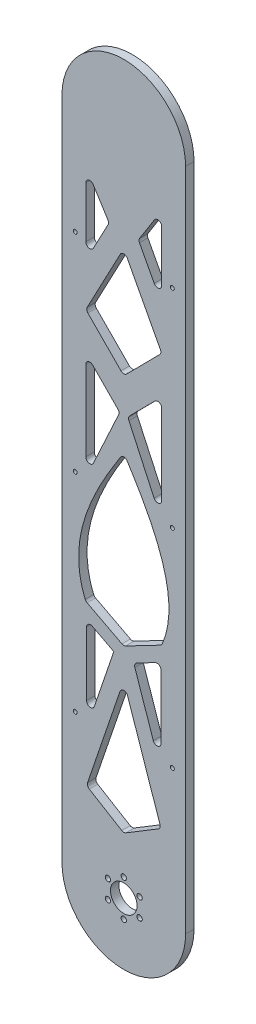
SolidWorks part; units mm, degrees
material "1060 Alloy"
ref_plane "Front Plane" through (0, 0, 0) normal (0, 0, 1) x (1, 0, 0)
ref_plane "Top Plane" through (0, 0, 0) normal (0, 1, 0) x (1, 0, 0)
ref_plane "Right Plane" through (0, 0, 0) normal (1, 0, 0) x (0, 0, -1)
sketch "Sketch2" plane through (0, 0, 0) normal (0, 0, 1) x (1, 0, 0)
  line L0 (0, 0) -> (0, 500) construction
  line L1 (-46.5, 0) -> (-46.5, 500)
  line L2 (46.5, 0) -> (46.5, 500)
  arc A0 (-46.5, 0) -> (46.5, 0) centre (0, 0) ccw
  arc A1 (46.5, 500) -> (-46.5, 500) centre (0, 500) ccw
  circle A2 centre (0, 500) radius 37.25 construction
  circle A3 centre (0, 0) radius 10
  circle A4 centre (0, 13.75) radius 2
  circle A5 centre (0, 0) radius 13.75 construction
  circle A6 centre (11.9078, 6.875) radius 2
  circle A7 centre (11.9078, -6.875) radius 2
  circle A8 centre (0, -13.75) radius 2
  circle A9 centre (-11.9078, -6.875) radius 2
  circle A10 centre (-11.9078, 6.875) radius 2
  point P3 (0, 250)
  point P27 (0, 0)
  dimension "D2" = 74.5
  dimension "D4" = 20
  dimension "D5" = 4
  dimension "D6" = 27.5
  dimension "D3" = 46.5
  dimension "D1" = 500
  dimension "D7" = 6
extrude "Boss-Extrude1" add sketch "Sketch2" along normal blind 6.35
sketch "Sketch4" plane through (0, 0, 6.35) normal (0, 0, 1) x (1, 0, 0)
  line L0 (0, 500) -> (0, 999.1647) construction
  line L29 (46.5, 500) -> (-46.5, 500) construction
  line L31 (28.0053, 59.376) -> (0, 42.4117)
  line L32 (0, 141.6934) -> (28.0053, 59.376)
  line L33 (-28.0053, 59.376) -> (0, 141.6934)
  line L34 (0, 42.4117) -> (-28.0053, 59.376)
  line L35 (-7.5, 156.9059) -> (-28.0053, 96.6336)
  line L36 (-28.0053, 167.5829) -> (-7.5, 156.9059)
  line L37 (-28.0053, 96.6336) -> (-28.0053, 167.5829)
  line L38 (28.0053, 167.5829) -> (7.5, 156.9059)
  line L39 (28.0053, 96.6336) -> (28.0053, 167.5829)
  line L40 (7.5, 156.9059) -> (28.0053, 96.6336)
  line L41 (0, 164.2751) -> (28.5505, 179.1412)
  line L42 (0, 164.2751) -> (-28.5505, 179.1412)
  line L43 (28.5505, 259.5868) -> (3, 314.9383)
  line L44 (28.5505, 340.7931) -> (28.5505, 259.5868)
  line L45 (3, 314.9383) -> (28.5505, 340.7931)
  line L46 (-3, 314.9383) -> (-28.5505, 340.7931)
  line L47 (-28.5505, 259.5868) -> (-3, 314.9383)
  line L48 (-28.5505, 340.7931) -> (-28.5505, 259.5868)
  line L49 (0, 423.1428) -> (-28.5505, 369.2462)
  line L50 (-28.5505, 369.2462) -> (0, 340.3557)
  line L51 (0, 340.3557) -> (28.5505, 369.2462)
  line L52 (0, 423.1428) -> (28.5505, 369.2462)
  line L53 (-28.5505, 462.0952) -> (-28.5505, 401.2902)
  line L54 (-11, 434.4215) -> (-28.5505, 462.0952)
  line L55 (-28.5505, 401.2902) -> (-11, 434.4215)
  line L56 (28.5505, 401.2902) -> (11, 434.4215)
  line L57 (28.5505, 462.0952) -> (28.5505, 401.2902)
  line L58 (11, 434.4215) -> (28.5505, 462.0952)
  arc A0 (46.5, 500) -> (-46.5, 500) centre (0, 500) ccw construction
  arc A1 (46.5, 500) -> (-46.5, 500) centre (0, 500) ccw construction
  spline S2 degree 3 poles (28.5505, 179.1412) (45.3203, 216.9857) (19.4301, 259.7903) (0, 290.0258) knots 0 0 0 0 1 1 1 1
  spline S3 degree 3 poles (-28.5505, 179.1412) (-45.3203, 216.9857) (-19.4301, 259.7903) (0, 290.0258) knots 0 0 0 0 1 1 1 1
extrude "Cut-Extrude1" cut sketch "Sketch4" against normal blind 10
fillet "Fillet3" radius 3 29 edges at (-11, 434.4215, 3.175) (-28.5505, 401.2902, 3.175) (28.5505, 401.2902, 3.175) (11, 434.4215, 3.175) (28.5505, 462.0952, 3.175) (-28.5505, 462.0952, 3.175) (0, 423.1428, 3.175) (-28.5505, 369.2462, 3.175) (28.5505, 369.2462, 3.175) (0, 340.3557, 3.175) (28.5505, 340.7931, 3.175) (-28.5505, 340.7931, 3.175) (-3, 314.9383, 3.175) (3, 314.9383, 3.175) (28.5505, 259.5868, 3.175) (-28.5505, 259.5868, 3.175) (28.5505, 179.1412, 3.175) (0, 290.0258, 3.175) (-28.5505, 179.1412, 3.175) (0, 164.2751, 3.175) (-28.0053, 96.6336, 3.175) (28.0053, 96.6336, 3.175) (7.5, 156.9059, 3.175) (-28.0053, 167.5829, 3.175) (28.0053, 167.5829, 3.175) (0, 141.6934, 3.175) (28.0053, 59.376, 3.175) (-28.0053, 59.376, 3.175) (0, 42.4117, 3.175)
sketch "Sketch5" plane through (0, 0, 6.35) normal (0, 0, 1) x (1, 0, 0)
  line L0 (0, -46.5) -> (108.8395, -46.5) construction
  line L1 (46.5, 100) -> (-46.5, 100) construction
  line L2 (46.5, 0) -> (46.5, 500) construction
  line L3 (-46.5, 500) -> (-46.5, 0) construction
  line L4 (-46.5, 106.35) -> (46.5, 106.35) construction
  line L5 (36.5, 106.35) -> (36.5, 100) construction
  line L6 (0, 106.35) -> (0, 100) construction
  line L7 (-46.5, 256.35) -> (46.5, 256.35) construction
  line L8 (-46.5, 181.35) -> (46.5, 181.35) construction
  line L9 (-46.5, 337.7) -> (46.5, 337.7) construction
  arc A1 (-46.5, 0) -> (46.5, 0) centre (0, 0) ccw construction
  circle A2 centre (36.5, 103.175) radius 1.5
  circle A3 centre (-36.5, 103.175) radius 1.5
  circle A4 centre (36.5, 259.525) radius 1.5
  circle A5 centre (-36.5, 259.525) radius 1.5
  circle A6 centre (36.5, 415.875) radius 1.5
  circle A7 centre (-36.5, 415.875) radius 1.5
  point P18 (36.5, 103.175)
  dimension "D2" = 3
  dimension "D1" = 146.5
  dimension "D3" = 10
  dimension "D4" = 6.35
  dimension "D5" = 150
  dimension "D6" = 81.35
  dimension "D7" = 81.35
extrude "Cut-Extrude2" cut sketch "Sketch5" against normal through all
equation "\"L1L\"=500"
equation "\"L1Thick\"=6.35"
equation "\"D1@Sketch2\"=\"L1L\""
equation "\"Harm-Drive-Outer\"=74.5"
equation "\"D2@Sketch2\"=\"Harm-Drive-Outer\""
equation "\"D1@Boss-Extrude1\"=\"L1Thick\""
